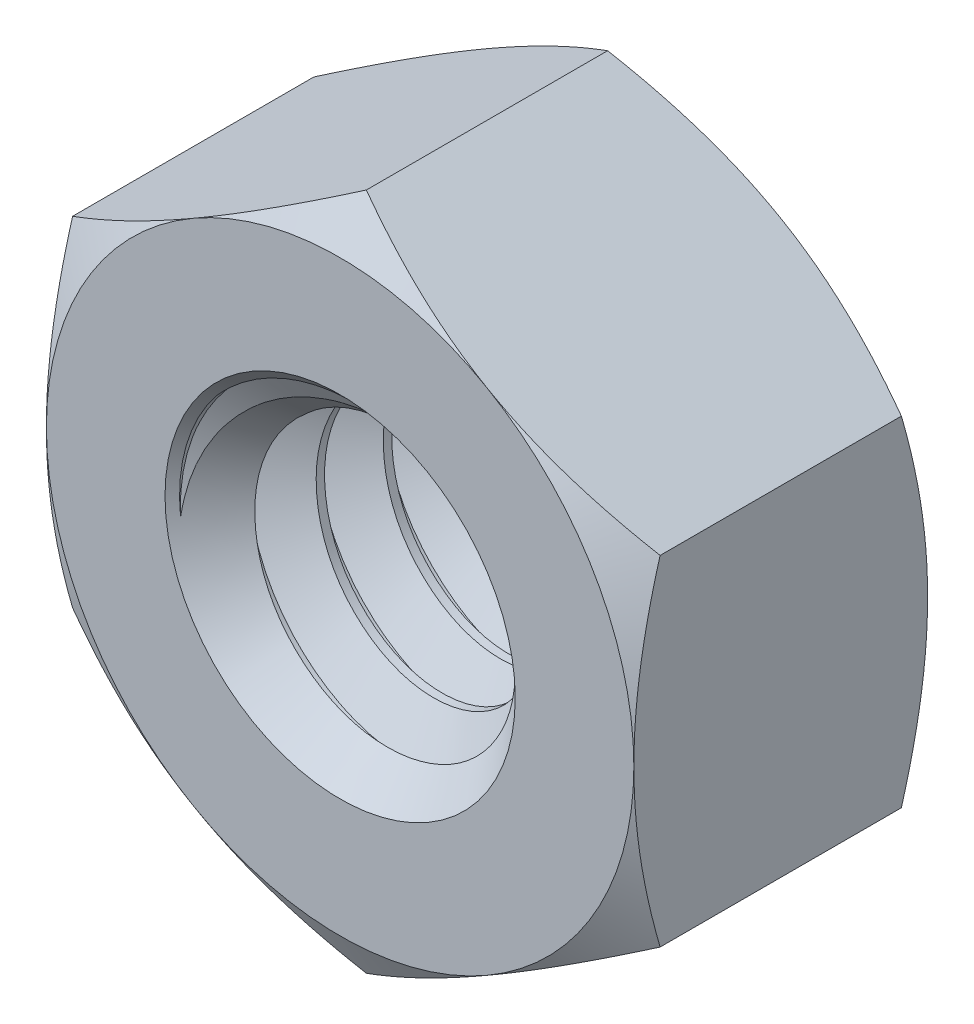
SolidWorks part; units mm, degrees
ref_plane "Front Plane" through (0, 0, 0) normal (0, 0, 1) x (1, 0, 0)
ref_plane "Top Plane" through (0, 0, 0) normal (0, 1, 0) x (1, 0, 0)
ref_plane "Right Plane" through (0, 0, 0) normal (1, 0, 0) x (0, 0, -1)
sketch "Sketch1" plane through (0, 0, 0) normal (0, 0, 1) x (1, 0, 0)
  line L1 (0, 6.4158) -> (-5.5563, 3.2079)
  line L2 (-5.5563, 3.2079) -> (-5.5563, -3.2079)
  line L3 (-5.5563, -3.2079) -> (0, -6.4158)
  line L4 (0, -6.4158) -> (5.5562, -3.2079)
  line L5 (5.5562, -3.2079) -> (5.5562, 3.2079)
  line L6 (5.5562, 3.2079) -> (0, 6.4158)
  circle A0 centre (0, 0) radius 5.5563 construction
  dimension "Width" = 11.1125
sketch "Sketch2" plane through (0, 0, 0) normal (1, 0, 0) x (0, 0, -1)
  line L0 (-2.7781, 0) -> (2.7781, 0) construction
  line L1 (-2.7781, 0) -> (-2.7781, 3.175)
  line L2 (-2.7781, 3.175) -> (2.7781, 3.175)
  line L3 (2.7781, 3.175) -> (2.7781, 0)
  line L4 (2.6987, 3.3125) -> (3.3337, 2.2126) construction
  line L5 (3.3337, 2.2126) -> (3.9688, 3.3125) construction
  line L6 (3.9688, 3.3125) -> (2.6987, 3.3125) construction
  line L7 (2.7384, 3.2437) -> (3.9291, 3.2437)
  line L8 (3.9291, 3.2437) -> (3.4131, 2.3501)
  line L9 (3.4131, 2.3501) -> (3.2544, 2.3501)
  line L10 (3.2544, 2.3501) -> (2.7384, 3.2437)
  line L11 (3.3338, 2.3501) -> (3.3337, 2.2126) construction
  line L12 (2.7781, 3.175) -> (3.8894, 3.175) construction
  line L13 (3.3337, 3.3125) -> (3.3337, 3.175) construction
  line L14 (-2.7781, -3.175) -> (2.7781, -3.175)
  line L15 (0, 5.5563) -> (0, -5.5563) construction
  line L16 (0, 5.5563) -> (0, -5.5563)
  point P2 (0, 0)
  point P18 (3.3338, 3.2437)
  point P22 (-2.7781, -3.175)
  point P23 (-2.7781, 5.5563)
  point P24 (2.7781, 5.5563)
  dimension "Thread Size" = 6.35
  dimension "Thread Pitch" = 1.27
  dimension "D2" = 0.1588
  dimension "Height" = 5.5562
sketch "Sketch3" plane through (0, 0, 0) normal (0, 0, 1) x (1, 0, 0)
  line L0 (5.5562, 3.2079) -> (0, 6.4158) construction
  line L1 (5.5562, -3.2079) -> (5.5562, 3.2079) construction
  line L2 (0, -6.4158) -> (5.5562, -3.2079) construction
  line L3 (-5.5563, -3.2079) -> (0, -6.4158) construction
  line L4 (-5.5563, 3.2079) -> (-5.5563, -3.2079) construction
  line L5 (0, 6.4158) -> (-5.5563, 3.2079) construction
  line L6 (5.5562, 3.2079) -> (0, 6.4158)
  line L7 (5.5562, -3.2079) -> (5.5562, 3.2079)
  line L8 (0, -6.4158) -> (5.5562, -3.2079)
  line L9 (-5.5563, -3.2079) -> (0, -6.4158)
  line L10 (-5.5563, 3.2079) -> (-5.5563, -3.2079)
  line L11 (0, 6.4158) -> (-5.5563, 3.2079)
extrude "Boss-Extrude1" add sketch "Sketch3" along normal up to vertex (2.7781 mm away) from vertex up to point (0, 0, 2.7781) starting at point (0, 0, -2.7781)
sketch "Sketch4" plane through (0, 0, 2.7781) normal (0, 0, 1) x (1, 0, 0)
  circle A0 centre (0, 0) radius 5.5563 construction
  circle A1 centre (0, 0) radius 5.5563
extrude "Cut-Extrude1" cut sketch "Sketch4" against normal through all draft 60 flip side to cut
sketch "Sketch5" plane through (0, 0, -2.7781) normal (0, 0, -1) x (-1, 0, 0)
  circle A0 centre (0, 0) radius 5.5563 construction
  circle A1 centre (0, 0) radius 5.5563
extrude "Cut-Extrude2" cut sketch "Sketch5" against normal through all draft 60 flip side to cut
sketch "Sketch6" plane through (0, 0, 0) normal (1, 0, 0) x (0, 0, -1)
  line L1 (-2.7781, 0) -> (2.7781, 0)
  line L2 (-2.7781, 0) -> (-2.7781, 3.175)
  line L3 (-2.7781, 3.175) -> (2.7781, 3.175)
  line L4 (2.7781, 0) -> (2.7781, 3.175)
revolve "Cut-Revolve1" cut sketch "Sketch6" angle 360 about L1
sketch "Sketch7" plane through (0, 0, -2.7781) normal (0, 0, -1) x (-1, 0, 0)
  circle A0 centre (0, 0) radius 3.175 construction
  circle A1 centre (0, 0) radius 3.175
curve "Helix/Spiral1" pitch 1.27 height 6.8262 radius 3.175 centre (0, 0, -2.7781) axis (0, 0, 1) start towards (0, 1, 0)
sketch "Sketch8" plane through (0, 0, 0) normal (1, 0, 0) x (0, 0, -1)
  line L0 (2.7384, 3.2437) -> (3.9291, 3.2437) construction
  line L1 (3.2544, 2.3501) -> (2.7384, 3.2437) construction
  line L2 (3.4131, 2.3501) -> (3.2544, 2.3501) construction
  line L3 (3.9291, 3.2437) -> (3.4131, 2.3501) construction
  line L4 (2.7384, 3.2437) -> (3.9291, 3.2437)
  line L5 (3.2544, 2.3501) -> (2.7384, 3.2437)
  line L6 (3.4131, 2.3501) -> (3.2544, 2.3501)
  line L7 (3.9291, 3.2437) -> (3.4131, 2.3501)
sweep "Sweep1" add profiles "Sketch8" path "Helix/Spiral1"
sketch "Sketch9" plane through (0, 0, -2.7781) normal (0, 0, -1) x (-1, 0, 0)
  circle A0 centre (0, 0) radius 3.3125
extrude "Cut-Extrude3" cut sketch "Sketch9" against normal through all draft 45 and the other way through all
sketch "Sketch10" plane through (0, 0, 2.7781) normal (0, 0, 1) x (1, 0, 0)
  circle A1 centre (0, 0) radius 3.3125
  circle A2 centre (0, 0) radius 3.3125
  dimension "D1" = 0
extrude "Cut-Extrude4" cut sketch "Sketch10" against normal through all draft 45 and the other way through all
equation "\"D2@Sketch2\" = \"Thread Pitch@Sketch2\" / 8"
equation "\"D4@Helix/Spiral1\" = \"Thread Pitch@Sketch2\""
equation "\"D3@Helix/Spiral1\"= \"Height@Sketch2\" + \"Thread Pitch@Sketch2\""
